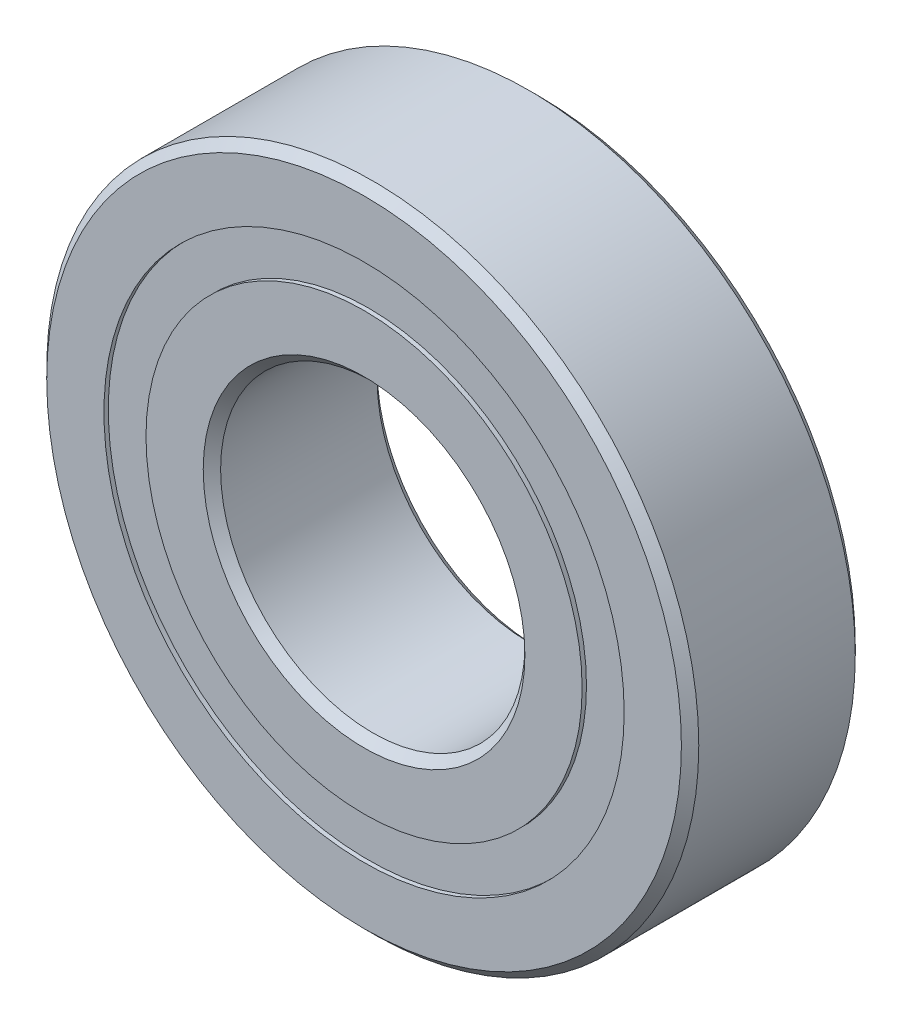
SolidWorks part; units mm, degrees
ref_plane "Front Plane" through (0, 0, 0) normal (0, 0, 1) x (1, 0, 0)
ref_plane "Top Plane" through (0, 0, 0) normal (0, 1, 0) x (1, 0, 0)
ref_plane "Right Plane" through (0, 0, 0) normal (1, 0, 0) x (0, 0, -1)
sketch "Sketch1" plane through (0, 0, 0) normal (1, 0, 0) x (0, 0, -1)
  line L0 (-6.35, 0) -> (6.35, 0) construction
  line L1 (0, 23.8125) -> (0, -23.8125) construction
  line L2 (5.715, 23.8125) -> (-5.715, 23.8125)
  line L3 (-5.715, 23.8125) -> (-6.35, 23.1775)
  line L4 (-6.35, 23.1775) -> (-6.35, 18.9977)
  line L5 (-6.35, 18.9977) -> (-2.8222, 18.9977)
  line L6 (6.35, 18.9977) -> (2.8222, 18.9977)
  line L7 (6.35, 23.1775) -> (6.35, 18.9977)
  line L8 (5.715, 23.8125) -> (6.35, 23.1775)
  line L9 (0, 23.8125) -> (0, 17.4625) construction
  line L10 (0, 17.4625) -> (0, 11.1125) construction
  arc A0 (-2.8222, 18.9977) -> (2.8222, 18.9977) centre (0, 17.4625) cw
  point P14 (0, 11.1125)
  dimension "Width" = 12.7
  dimension "OD" = 47.625
  dimension "D1" = 45
  dimension "D2" = 0.635
  dimension "Shaft Dia" = 22.225
  dimension "D3" = 5.6444
  dimension "D4" = 1.5352
revolve "Revolve1" add sketch "Sketch1" angle 360 about L0
sketch "Sketch3" plane through (0, 0, 0) normal (1, 0, 0) x (0, 0, -1)
  line L0 (-6.35, 15.9273) -> (-2.8222, 15.9273)
  line L1 (0, 23.8125) -> (0, -23.8125) construction
  line L2 (-6.35, 23.1775) -> (-6.35, 18.9977) construction
  line L3 (-6.35, 15.9273) -> (-6.35, 11.7475)
  line L4 (-5.715, 23.8125) -> (-6.35, 23.1775) construction
  line L5 (-6.35, 11.7475) -> (-5.715, 11.1125)
  line L6 (-5.715, 11.1125) -> (5.715, 11.1125)
  line L7 (5.715, 23.8125) -> (5.715, -23.8125) construction
  line L8 (5.715, 11.1125) -> (6.35, 11.7475)
  line L9 (6.35, -23.1775) -> (6.35, 23.1775) construction
  line L10 (6.35, 11.7475) -> (6.35, 15.9273)
  line L11 (6.35, 15.9273) -> (2.8222, 15.9273)
  line L13 (5.715, 23.8125) -> (6.35, 23.1775) construction
  arc A0 (2.8222, 18.9977) -> (-2.8222, 18.9977) centre (0, 17.4625) ccw construction
  arc A1 (2.8222, 15.9273) -> (-2.8222, 15.9273) centre (0, 17.4625) cw
revolve "Revolve3" add sketch "Sketch3" angle 360 about L0
sketch "Sketch4" plane through (0, 0, 0) normal (1, 0, 0) x (0, 0, -1)
  line L0 (-3.2127, 17.4625) -> (3.2127, 17.4625)
  arc A2 (-3.2127, 17.4625) -> (3.2127, 17.4625) centre (0, 17.4625) cw
  arc A3 (2.8222, 18.9977) -> (-2.8222, 18.9977) centre (0, 17.4625) ccw construction
revolve "Revolve4" add sketch "Sketch4" angle 360 about L0
ref_axis "Axis1" through (0, 0, -6.35) along (0, 0, 1)
pattern_circular "CirPattern1" count 12 every 30 about axis through (0, 0, -6.35) along (0, 0, 1) of bodies 104
sketch "Sketch5" plane through (0, 0, 0) normal (1, 0, 0) x (0, 0, -1)
  line L0 (-6.35, 18.9977) -> (-2.8222, 18.9977) construction
  line L1 (-6.0325, 18.9977) -> (-3.2127, 18.9977)
  line L2 (-6.0325, 18.9977) -> (-6.0325, 15.9273)
  line L3 (-6.0325, 15.9273) -> (-3.2127, 15.9273)
  line L4 (-3.2127, 18.9977) -> (-3.2127, 15.9273)
  line L5 (-6.35, 15.9273) -> (-2.8222, 15.9273) construction
  line L6 (6.35, 18.9977) -> (2.8222, 18.9977) construction
  line L7 (6.0325, 18.9977) -> (3.2127, 18.9977)
  line L8 (6.0325, 18.9977) -> (6.0325, 15.9273)
  line L9 (6.0325, 15.9273) -> (3.2127, 15.9273)
  line L10 (3.2127, 18.9977) -> (3.2127, 15.9273)
  line L11 (6.35, 15.9273) -> (2.8222, 15.9273) construction
  line L12 (-5.715, 23.8125) -> (-6.35, 23.1775) construction
  point P18 (-6.0325, 23.495)
revolve "Revolve5" add sketch "Sketch5" angle 360 about L0
equation "\"D2@Sketch1\" = \"Width@Sketch1\"*.05"
equation "\"D3@Sketch1\" = \"Width@Sketch1\"/2.25"
equation "\"D4@Sketch1\" = (((\"OD@Sketch1\"-\"Width@Sketch1\")/2)/3.25)/3.5"
equation "\"D2@CirPattern1\" = 360/\"Balls@CirPattern1\""
